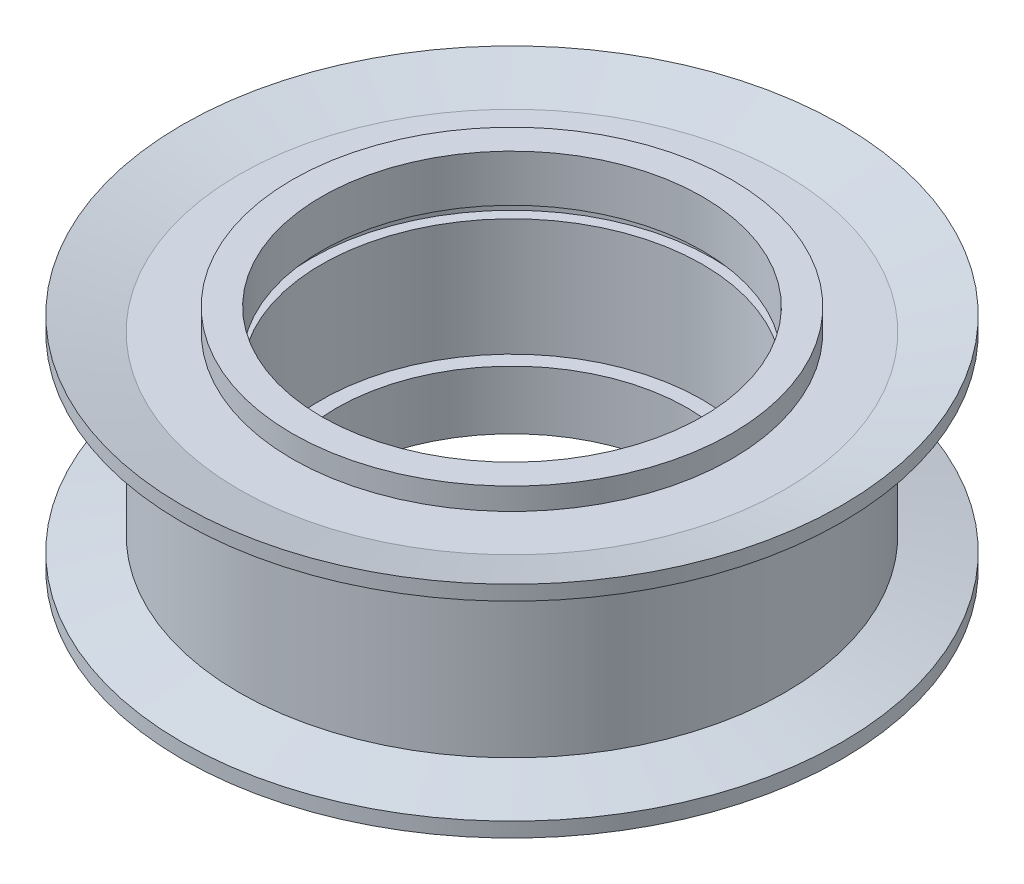
SolidWorks part; units mm, degrees
material "6061 合金"
ref_plane "前基準面" through (0, 0, 0) normal (0, 0, 1) x (1, 0, 0)
ref_plane "上基準面" through (0, 0, 0) normal (0, 1, 0) x (1, 0, 0)
ref_plane "右基準面" through (0, 0, 0) normal (1, 0, 0) x (0, 0, -1)
sketch "草圖1" plane through (0, 0, 0) normal (0, 0, 1) x (1, 0, 0)
  line L0 (0, 49.34) -> (0, -26.8952) construction
  line L1 (18.62, 0) -> (6.3419, 0) construction
  line L2 (13, 4) -> (13, -4)
  line L3 (12, -8) -> (12, -4)
  line L4 (13, 4.8) -> (13.7129, 4.8)
  line L5 (18.62, 5.5) -> (15, 5.5)
  line L6 (15, 8) -> (15, 5.5)
  line L8 (19.1, 5.5) -> (19.1, -5.5) construction
  line L9 (18.62, -5.5) -> (18.62, 5.5)
  line L10 (15, -5.5) -> (18.62, -5.5)
  line L11 (15, 8) -> (13, 8)
  line L12 (15, -8) -> (15, -5.5)
  line L13 (12, -4) -> (13, -4)
  line L14 (13, 8) -> (13, 4.8)
  line L15 (13, 4) -> (13.7129, 4)
  line L16 (13.7129, 4.8) -> (13.7129, 4)
  line L20 (15, -8) -> (12, -8)
  dimension "D2" = 24
  dimension "D3" = 37.24
  dimension "D4" = 26
  dimension "D5" = 4
  dimension "D6" = 11
  dimension "D7" = 30
  dimension "D8" = 16
  dimension "D9" = 3
  dimension "D10" = 8
  dimension "D11" = 0.8
  dimension "D12" = 38.2
  dimension "D15" = 3.62
revolve "旋轉1" add sketch "草圖1" angle 360 about L0
sketch "草圖7" plane through (0, 0, 0) normal (0, 0, 1) x (1, 0, 0)
  line L0 (0, 0) -> (0, 8) construction
  line L1 (15, 8) -> (-15, 8) construction
  line L3 (-18.62, -5.5) -> (18.62, -5.5) construction
  line L5 (-15, -5.5) -> (-15, -8) construction
  line L8 (0, 0) -> (-16, 0) construction
  line L12 (-22.5, -6.5) -> (-18.62, -5.5)
  line L13 (-22.5, -7.5) -> (-22.5, -6.5)
  line L14 (-22.5, -7.5) -> (-18.62, -6.5)
  line L15 (-15, -5.5) -> (-15, -6.5)
  line L16 (-18.62, -6.5) -> (-15, -6.5)
  line L17 (-18.62, -5.5) -> (-15, -5.5)
  dimension "D1" = 45
  dimension "D2" = 1
  dimension "D3" = 1
revolve "旋轉2" add sketch "草圖7" angle 360 about L0
mirror "鏡射1" about plane through (0, 0, 0) normal (0, 1, 0) of "旋轉2"
ref_plane "平面1" through (0, 0, 18.62) normal (0, 0, 1) x (1, 0, 0)
ref_axis "基準軸1" through (0, -8, 0) along (0, 1, 0)
